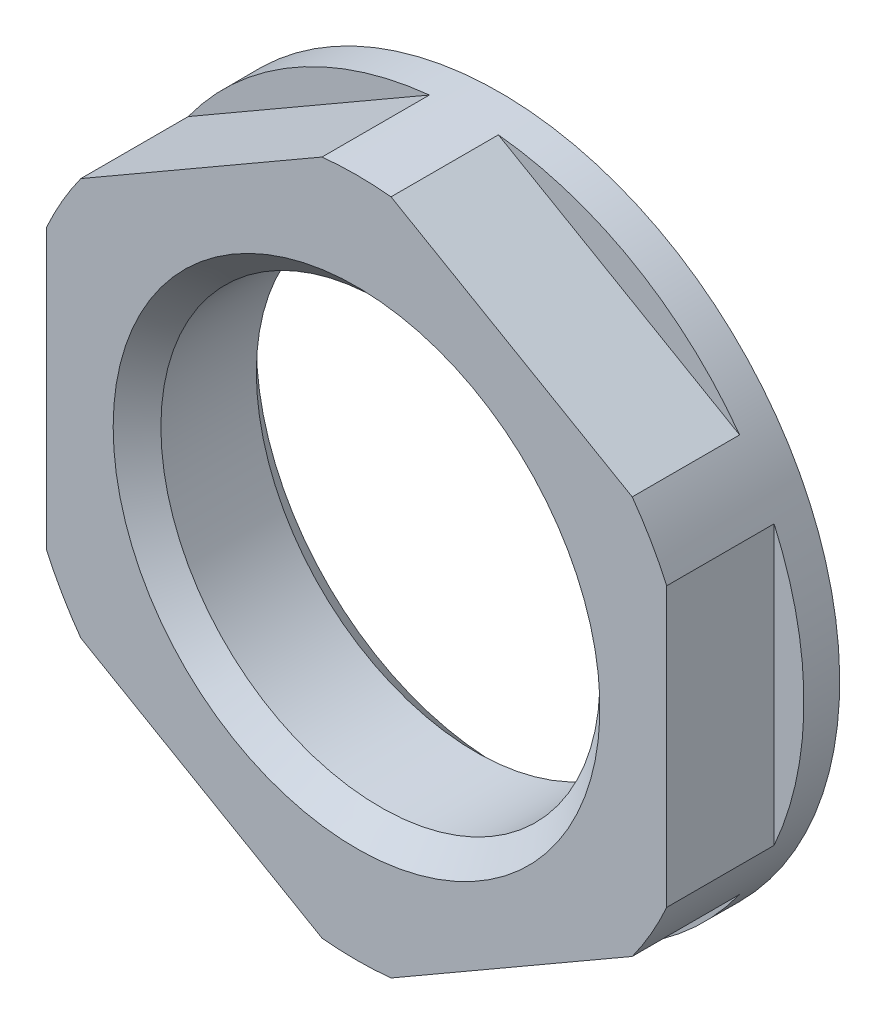
SolidWorks part; units mm, degrees
ref_plane "Спереди" through (0, 0, 0) normal (0, 0, 1) x (1, 0, 0)
ref_plane "Сверху" through (0, 0, 0) normal (0, 1, 0) x (1, 0, 0)
ref_plane "Справа" through (0, 0, 0) normal (1, 0, 0) x (0, 0, -1)
sketch "Эскиз1" plane through (0, 0, 0) normal (0, 0, 1) x (1, 0, 0)
  line L0 (0, 15.0111) -> (0, -15.0111) construction
  line L1 (0, 15.0111) -> (-13, 7.5056)
  line L2 (-13, 7.5056) -> (-13, -7.5056)
  line L3 (-13, -7.5056) -> (0, -15.0111)
  line L4 (0, -15.0111) -> (13, -7.5056)
  line L5 (13, -7.5056) -> (13, 7.5056)
  line L6 (13, 7.5056) -> (0, 15.0111)
  line L7 (13, -7.5056) -> (-13, -7.5056) construction
  dimension "D1" = 120
  dimension "D2" = 26
extrude "Вытянуть1" add sketch "Эскиз1" along normal blind 6
sketch "Эскиз2" plane through (0, 0, 6) normal (0, 0, 1) x (1, 0, 0)
  circle A0 centre (0, 0) radius 15.0111
  circle A1 centre (0, 0) radius 14.25
  dimension "D1" = 28.5
extrude "Вырез-Вытянуть1" cut sketch "Эскиз2" against normal through all
sketch "Эскиз4" plane through (0, 0, 0) normal (0, 0, -1) x (-1, 0, 0)
  circle A0 centre (0, 0) radius 14.25
  arc A1 (13, 5.8363) -> (11.5544, 8.3402) centre (0, 0) ccw construction
extrude "Вытянуть3" add sketch "Эскиз4" against normal blind 1.5
sketch "Эскиз5" plane through (0, 0, 6) normal (0, 0, 1) x (1, 0, 0)
  circle A0 centre (0, 0) radius 9.2
  dimension "D1" = 18.4
extrude "Вырез-Вытянуть2" cut sketch "Эскиз5" against normal through all
chamfer "Фаска1" distance 1 angle 45 2 edges at (9.2, 0, 0) (9.2, 0, 6)
